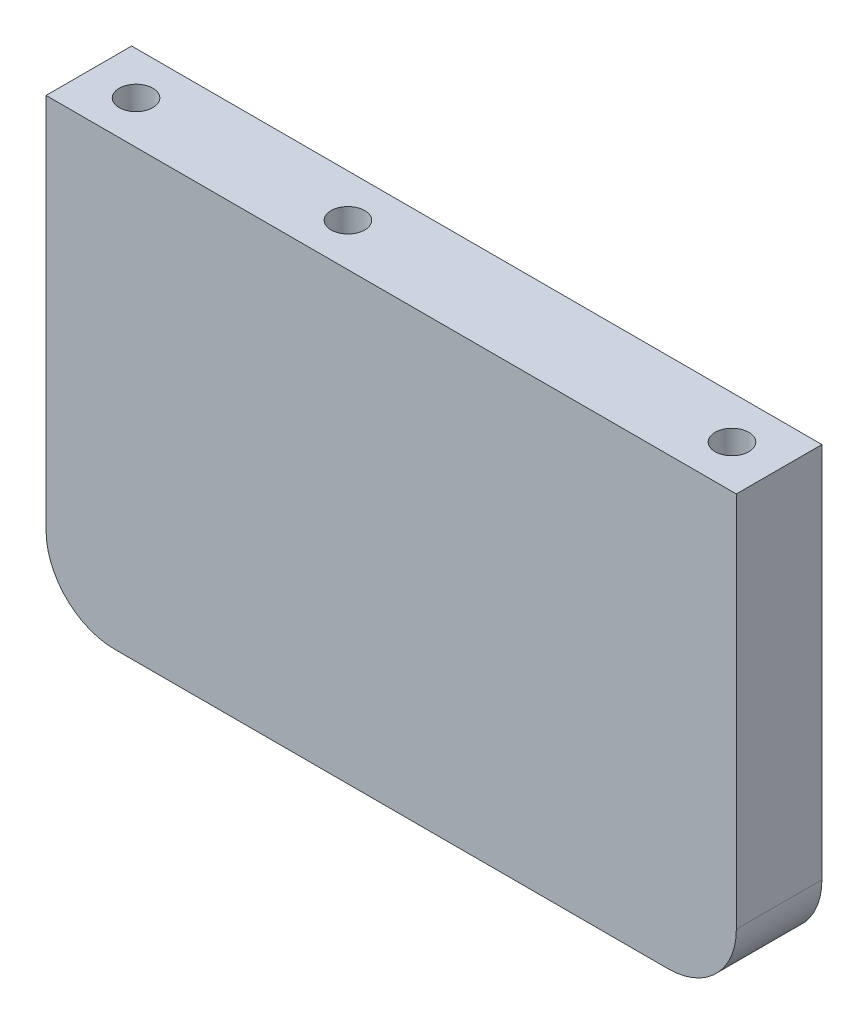
SolidWorks part; units mm, degrees
ref_plane "Front Plane" through (0, 0, 0) normal (0, 0, 1) x (1, 0, 0)
ref_plane "Top Plane" through (0, 0, 0) normal (0, 1, 0) x (1, 0, 0)
ref_plane "Right Plane" through (0, 0, 0) normal (1, 0, 0) x (0, 0, -1)
sketch "Sketch1" plane through (0, 0, 451.9384) normal (0, 0, 1) x (1, 0, 0)
  line L10 (-33.225, 19.05) -> (18, 19.05)
  line L11 (-33.225, 19.05) -> (-33.225, -14)
  line L12 (-33.225, -14) -> (18, -14)
  line L13 (18, 19.05) -> (18, -14)
  circle A2 centre (0, 0) radius 11.05 construction
  circle A3 centre (-22.225, 0) radius 3.556 construction
  dimension "D2" = 7.112
  dimension "D5" = 19.05
  dimension "D6" = 11
  dimension "D3" = 22.225
  dimension "D1" = 22.1
  dimension "D8" = 51.225
  dimension "D4" = 14
  dimension "D7" = 18
extrude "Boss-Extrude1" add sketch "Sketch1" against normal blind 6.35
sketch "Sketch8" plane through (0, 19.05, 0) normal (0, 1, 0) x (1, 0, 0)
  line L0 (-33.225, -448.7634) -> (18, -448.7634) construction
  line L1 (-33.225, -445.5884) -> (-33.225, -451.9384) construction
  line L2 (18, -445.5884) -> (18, -451.9384) construction
  circle A1 centre (-29.725, -448.7634) radius 1.25
  circle A2 centre (-14, -448.7634) radius 1.25
  circle A3 centre (14.5, -448.7634) radius 1.25
  dimension "D1" = 2.5
  dimension "D2" = 3.5
  dimension "D3" = 3.5
  dimension "D4" = 14
extrude "Cut-Extrude4" cut sketch "Sketch8" against normal blind 15
fillet "Fillet3" radius 5.08 2 edges at (18, -14, 448.7634) (-33.225, -14, 448.7634)
sketch "Sketch10" plane through (0, 0, 445.5884) normal (0, 0, -1) x (-1, 0, 0)
  circle A0 centre (22.225, 0) radius 3.556 construction
  circle A1 centre (0, 0) radius 11.05 construction
  circle A2 centre (22.225, 0) radius 3.556
  circle A3 centre (0, 0) radius 11.05
extrude "Cut-Extrude5" cut sketch "Sketch10" against normal offset from surface (4.7625 mm away) 1.5875 up to face at (-7.6125, -1.6407, 451.9384)
